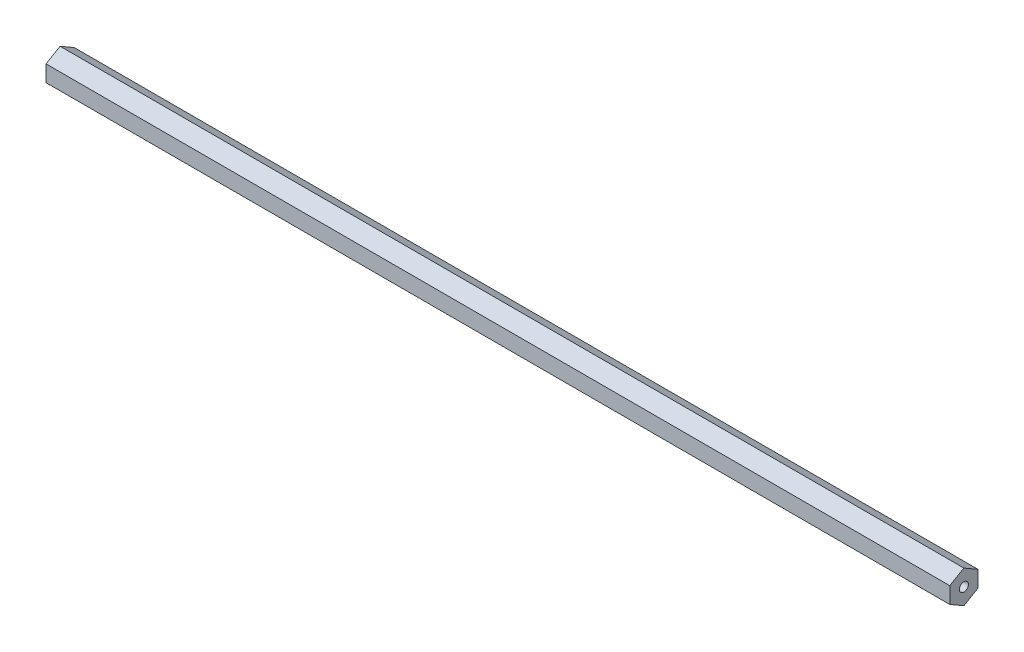
SolidWorks part; units mm, degrees
material "7075-T6 (SN)"
ref_plane "Front Plane" through (0, 0, 0) normal (0, 0, 1) x (1, 0, 0)
ref_plane "Top Plane" through (0, 0, 0) normal (0, 1, 0) x (1, 0, 0)
ref_plane "Right Plane" through (0, 0, 0) normal (1, 0, 0) x (0, 0, -1)
sketch "Sketch1" plane through (0, 0, 0) normal (1, 0, 0) x (0, 0, -1)
  line L1 (0, 7.3323) -> (-6.35, 3.6662)
  line L2 (-6.35, 3.6662) -> (-6.35, -3.6662)
  line L3 (-6.35, -3.6662) -> (0, -7.3323)
  line L4 (0, -7.3323) -> (6.35, -3.6662)
  line L5 (6.35, -3.6662) -> (6.35, 3.6662)
  line L6 (6.35, 3.6662) -> (0, 7.3323)
  circle A2 centre (0, 0) radius 6.35 construction
  dimension "D2" = 12.7
extrude "Boss-Extrude1" add sketch "Sketch1" along normal mid plane 406.4 contours L5 L6 L1 L2 L3 L4 region at (0, 0, 0)
sketch "Sketch3" plane through (-200.025, 0, 0) normal (-1, 0, 0) x (0, 0, 1)
  circle A0 centre (0, 0) radius 6.35
  dimension "D1" = 12.7
hole_wizard "#10-32 Tapped Hole1" positions "3DSketch1" profile "Sketch4" tap size "#10-32" standard "ANSI Inch"
sketch3d "3DSketch1"
  point P10 (203.2, 0, 0)
  point P13 (-203.2, 0, 0)
sketch "Sketch4" plane through (203.2, 0, 0) normal (0, 1, 0) x (0, 0, -1)
  line L0 (0, 0) -> (0, 17.5608)
  line L1 (0, 17.5608) -> (2.0193, 16.3474)
  line L2 (2.0193, 16.3474) -> (2.0193, 0)
  line L5 (2.0193, 0) -> (0, 0)
  line L10 (0, 17.5608) -> (-2.0193, 16.3474) construction
  line L11 (0, -6.35) -> (0, 107.95) construction
  dimension "Tap Drill Dia." = 4.0386
  dimension "Tap Drill Depth" = 16.3474
  dimension "Drill Angle" = 118
cosmetic thread "Hole Thread1" parameters "D1"=13.97, "D2"=4.826
cosmetic thread "Hole Thread2" parameters "D1"=13.97, "D2"=4.826
